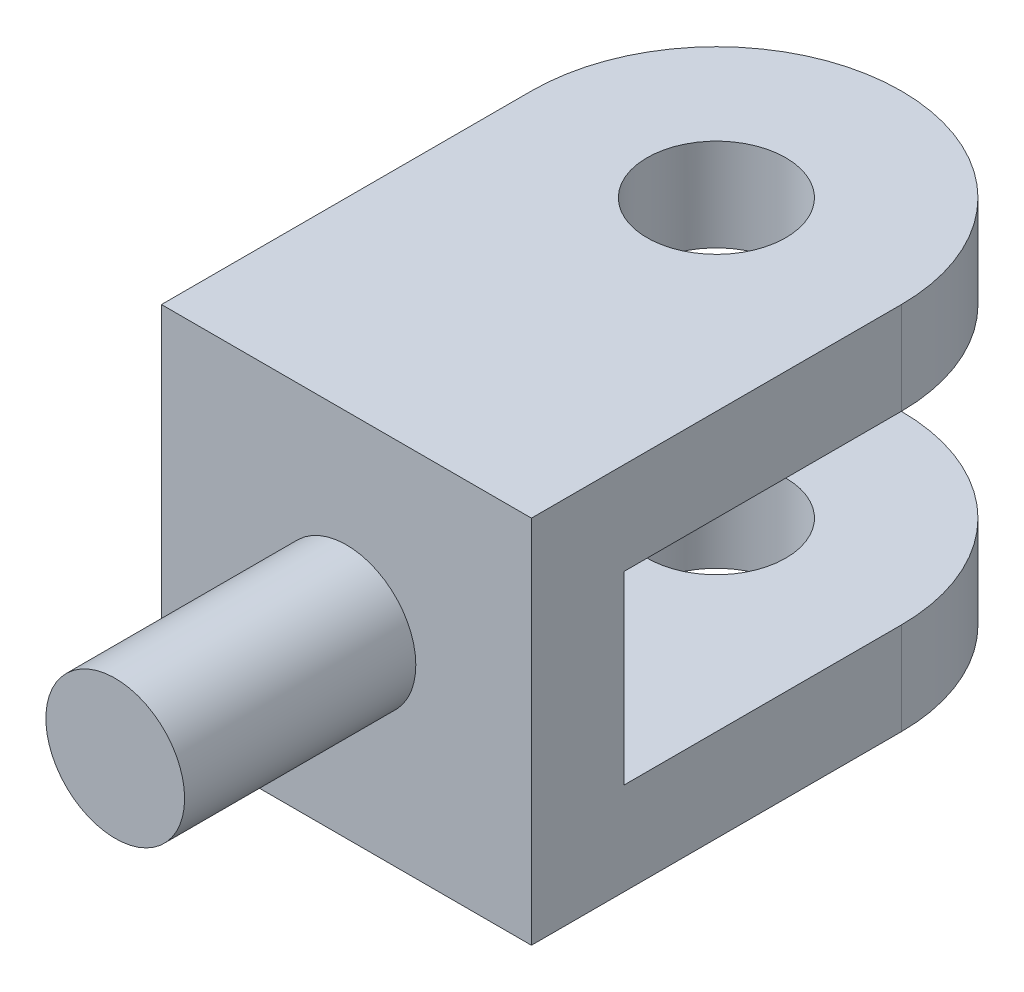
SolidWorks part; units mm, degrees
ref_plane "Front Plane" through (0, 0, 0) normal (0, 0, 1) x (1, 0, 0)
ref_plane "Top Plane" through (0, 0, 0) normal (0, 1, 0) x (1, 0, 0)
ref_plane "Right Plane" through (0, 0, 0) normal (1, 0, 0) x (0, 0, -1)
sketch "Sketch1" plane through (0, 0, 0) normal (0, 0, 1) x (1, 0, 0)
  line L1 (-8, 8) -> (8, 8)
  line L2 (-8, 8) -> (-8, -8)
  line L3 (-8, -8) -> (8, -8)
  line L4 (8, 8) -> (8, -8)
  line L5 (-8, 8) -> (8, -8) construction
  line L6 (-8, -8) -> (8, 8) construction
  point P0 (0, 0)
  dimension "D1" = 16
  dimension "D2" = 16
extrude "Boss-Extrude1" add sketch "Sketch1" along normal blind 24
sketch "Sketch3" plane through (0, 0, 24) normal (0, 0, 1) x (1, 0, 0)
  circle A0 centre (0, 0) radius 3
  dimension "D1" = 6
extrude "Boss-Extrude2" add sketch "Sketch3" along normal blind 10
sketch "Sketch4" plane through (-8, 0, 0) normal (-1, 0, 0) x (0, 0, 1)
  line L0 (24, 8) -> (0, 8) construction
  line L1 (20, 4) -> (0, 4)
  line L2 (20, 4) -> (20, -4)
  line L3 (20, -4) -> (0, -4)
  line L4 (0, 4) -> (0, -4)
  line L5 (24, -3) -> (24, 3) construction
  line L6 (0, 8) -> (0, -8) construction
  point P8 (0, 0)
  dimension "D1" = 8
  dimension "D2" = 4
  dimension "D3" = 4
  dimension "D4" = 0
extrude "Cut-Extrude1" cut sketch "Sketch4" against normal through all
sketch "Sketch5" plane through (0, -8, 0) normal (0, -1, 0) x (1, 0, 0)
  line L0 (-8, 24) -> (8, 24) construction
  circle A0 centre (0, 8) radius 3
  dimension "D1" = 6
  dimension "D2" = 16
extrude "Cut-Extrude2" cut sketch "Sketch5" against normal through all
fillet "Fillet1" radius 8 4 edges at (-8, 6, 0) (8, 6, 0) (8, -6, 0) (-8, -6, 0)
